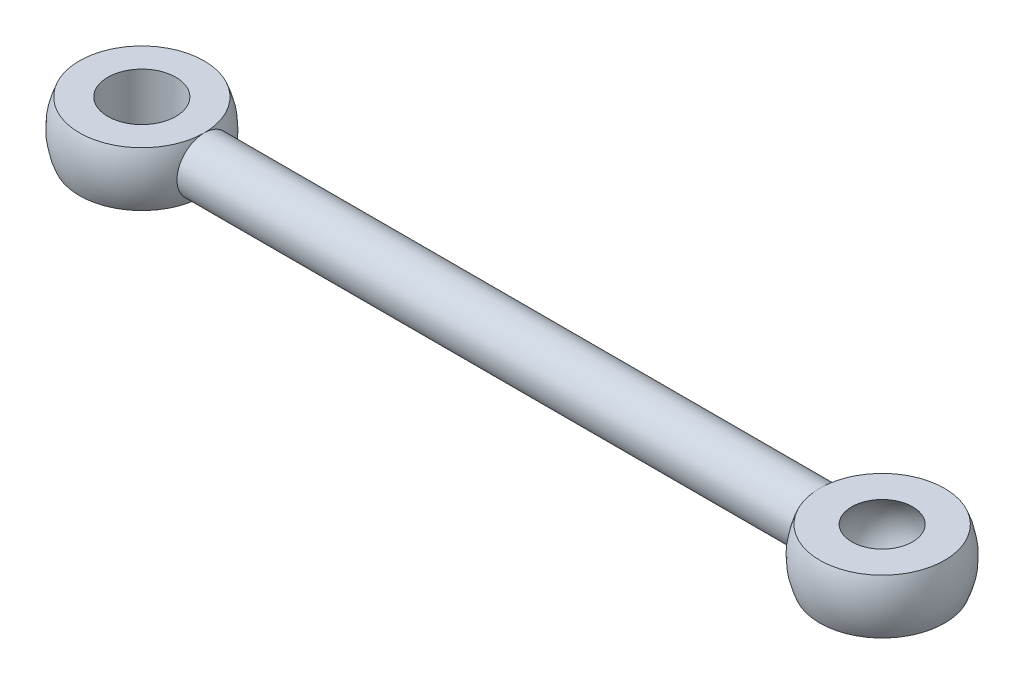
SolidWorks part; units mm, degrees
material "Alloy Steel"
ref_plane "Ön Düzlem" through (0, 0, 0) normal (0, 0, 1) x (1, 0, 0)
ref_plane "Üst Düzlem" through (0, 0, 0) normal (0, 1, 0) x (1, 0, 0)
ref_plane "Sağ Düzlem" through (0, 0, 0) normal (1, 0, 0) x (0, 0, -1)
sketch "Sketch1" plane through (0, 0, 0) normal (0, 0, 1) x (1, 0, 0)
  line L0 (40.6984, 0) -> (-23.7016, 0)
  line L2 (-14.119, 2) -> (31.1159, 2)
  arc A0 (-14.119, 2) -> (-23.7016, 0) centre (-18.7016, 0) ccw
  arc A4 (40.6984, 0) -> (31.1159, 2) centre (35.6984, 0) ccw
  dimension "D1" = 5
  dimension "D3" = 2
  dimension "D4" = 64.4
  dimension "D2" = 5
revolve "Revolve1" add sketch "Sketch1" angle 360 about L0
sketch "Sketch7" plane through (0, 0, 0) normal (0, 0, 1) x (1, 0, 0)
  line L1 (31.1159, 2) -> (-14.119, 2) construction
  line L3 (31.1159, 2) -> (31.1159, -2) construction
  line L5 (31.1159, 2) -> (40.281, 2)
  line L6 (31.1159, -2) -> (40.281, -2)
  arc A0 (40.281, 2) -> (31.1159, 2) centre (35.6984, 0) ccw
  arc A1 (31.1159, -2) -> (40.281, -2) centre (35.6984, 0) ccw
extrude "Cut-Extrude5" cut sketch "Sketch7" against normal blind 30 and the other way blind 30
sketch "Sketch9" plane through (0, 0, 0) normal (0, 1, 0) x (1, 0, 0)
  line L0 (35.6984, 3) -> (35.6984, -3)
  arc A0 (35.6984, -3) -> (35.6984, 3) centre (35.6984, 0) ccw
  dimension "D1" = 6
revolve "Cut-Revolve8" cut sketch "Sketch9" angle 360 about L0
sketch "Sketch12" plane through (0, 0, 0) normal (0, 0, 1) x (1, 0, 0)
  line L1 (31.1159, 2) -> (-14.119, 2) construction
  line L3 (-14.119, 2) -> (-14.119, -2) construction
  line L6 (-14.119, 2) -> (-23.2841, 2)
  line L7 (-14.119, -2) -> (-23.2841, -2)
  arc A0 (-23.2841, -2) -> (-14.119, -2) centre (-18.7016, 0) ccw
  arc A1 (-14.119, 2) -> (-23.2841, 2) centre (-18.7016, 0) ccw
extrude "Cut-Extrude6" cut sketch "Sketch12" against normal blind 30 and the other way blind 30
sketch "Sketch14" plane through (0, 2, 0) normal (0, 1, 0) x (1, 0, 0)
  circle A2 centre (-18.7016, 0) radius 2.5
  dimension "D1" = 5
extrude "Cut-Extrude7" cut sketch "Sketch14" against normal blind 30
